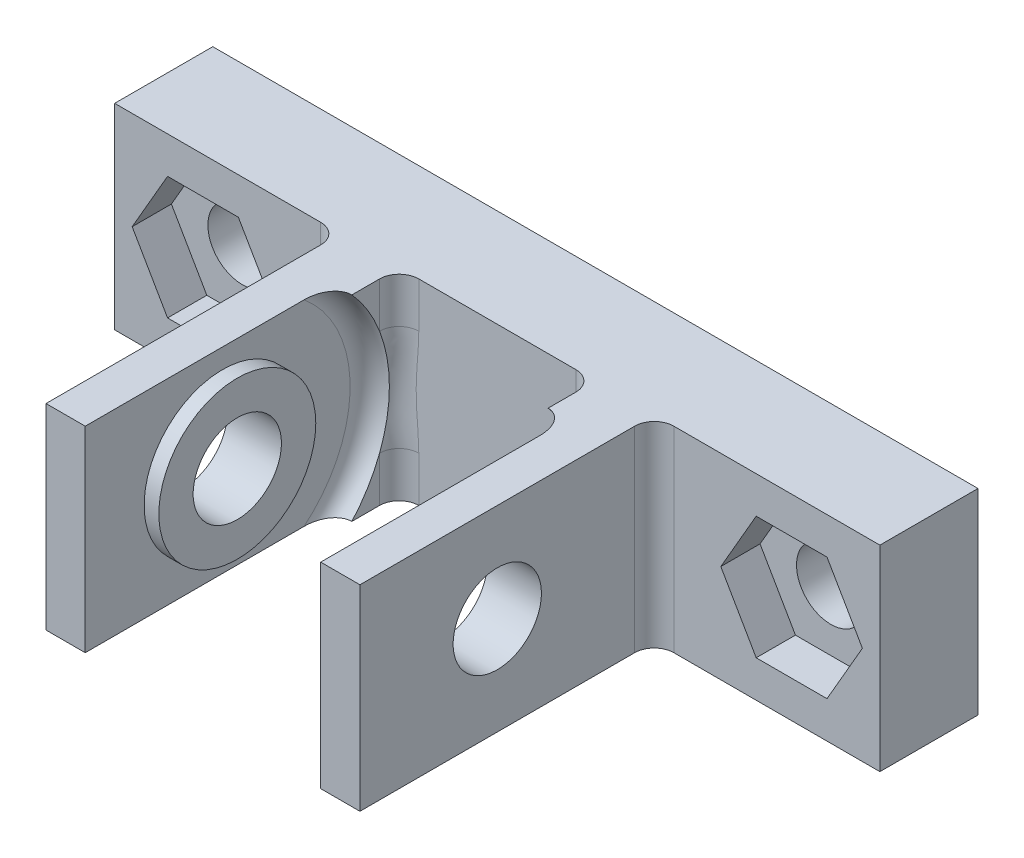
SolidWorks part; units mm, degrees
ref_plane "Front Plane" through (0, 0, 0) normal (0, 0, 1) x (1, 0, 0)
ref_plane "Top Plane" through (0, 0, 0) normal (0, 1, 0) x (1, 0, 0)
ref_plane "Right Plane" through (0, 0, 0) normal (1, 0, 0) x (0, 0, -1)
sketch "Sketch1" plane through (0, 0, 0) normal (0, 1, 0) x (1, 0, 0)
  line L0 (0, 0) -> (0, -20.0709) construction
  line L1 (-8, 0) -> (8, 0)
  line L2 (8, 0) -> (8, -20)
  line L3 (8, -20) -> (5, -20)
  line L4 (5, -20) -> (5, -5)
  line L5 (5, -5) -> (-5, -5)
  line L6 (-5, -20) -> (-5, -5)
  line L7 (-8, -20) -> (-5, -20)
  line L8 (-8, 0) -> (-8, -20)
  line L9 (5, -20) -> (5, -5)
  point P9 (0, -5)
  dimension "D1" = 5
  dimension "D2" = 3
  dimension "D3" = 15
  dimension "D4" = 5
extrude "Boss-Extrude1" add sketch "Sketch1" along normal blind 10 contours L1 L0 L5 L4 L3 L2 | L0 L1 L8 L7 L6 L5 region at (5.3235, 0, 7.7941) region at (-5.3235, 0, 7.7941)
sketch "Sketch2" plane through (8, 0, 0) normal (1, 0, 0) x (0, 0, -1)
  line L0 (-20, 5) -> (0, 5) construction
  line L1 (-20, 10) -> (-20, 0) construction
  line L2 (0, 10) -> (0, 0) construction
  circle A0 centre (-13, 5) radius 2.25
  dimension "D1" = 4.5
  dimension "D2" = 13
extrude "Cut-Extrude1" cut sketch "Sketch2" against normal through all contours A0
sketch "Sketch3" plane through (0, 10, 0) normal (0, 1, 0) x (1, 0, 0)
  line L1 (-19.5, -5) -> (19.5, -5)
  line L2 (0, 0) -> (0, -5) construction
  line L3 (-19.5, 0) -> (19.5, 0)
  line L4 (19.5, -5) -> (19.5, 0)
  line L5 (-8, 0) -> (8, 0) construction
  line L7 (-19.5, -5) -> (-19.5, 0)
  line L8 (5, -5) -> (-5, -5) construction
  dimension "D1" = 19.5
extrude "Boss-Extrude2" add sketch "Sketch3" against normal through all
sketch "Sketch4" plane through (0, 0, 5) normal (0, 0, 1) x (1, 0, 0)
  line L0 (-19.5, 5) -> (-8, 5) construction
  line L1 (-19.5, 0) -> (-19.5, 10) construction
  line L2 (-8, 10) -> (-8, 0) construction
  line L3 (-15, 0) -> (-15, 10) construction
  line L6 (0, 0) -> (0, 10) construction
  line L7 (5, 0) -> (-5, 0) construction
  line L8 (5, 10) -> (-5, 10) construction
  line L9 (15, 0) -> (15, 10) construction
  line L10 (19.5, 5) -> (8, 5) construction
  line L11 (-15, 0) -> (-15, 10) construction
  circle A0 centre (-15, 5) radius 1.75
  circle A1 centre (15, 5) radius 1.75
  dimension "D1" = 3.5
  dimension "D2" = 15
extrude "Cut-Extrude2" cut sketch "Sketch4" against normal through all
sketch "Sketch6" plane through (-5, 0, 0) normal (1, 0, 0) x (0, 0, -1)
  line L0 (-13, 12.5) -> (-20.5, 12.5)
  line L1 (-20.5, 12.5) -> (-20.5, 5)
  line L2 (-20.5, 5) -> (-20.5, -2.5)
  line L3 (-20.5, -2.5) -> (-13, -2.5)
  arc A0 (-13, -2.5) -> (-13, 12.5) centre (-13, 5) ccw
  circle A1 centre (-13, 5) radius 2.25 construction
  dimension "D1" = 15
extrude "Cut-Extrude3" cut sketch "Sketch6" against normal blind 1
sketch "Sketch5" plane through (-6, 0, 0) normal (1, 0, 0) x (0, 0, -1)
  circle A0 centre (-13, 5) radius 4
  circle A1 centre (-13, 5) radius 2.25
  circle A2 centre (-13, 5) radius 2.25 construction
  dimension "D1" = 8
extrude "Boss-Extrude3" add sketch "Sketch5" along normal blind 0.75
mirror "Mirror1" about plane through (0, 0, 0) normal (1, 0, 0) of "Boss-Extrude3", "Cut-Extrude3"
fillet "Fillet1" radius 1 6 edges at (-6, 5, 5.5) (6, 5, 5.5) (5, 5, 5) (-5, 5, 5) (8, 5, 5) (-8, 5, 5)
sketch "Sketch7" plane through (0, 0, 5) normal (0, 0, 1) x (1, 0, 0)
  line L0 (0, 10) -> (0, 0) construction
  line L1 (16.8042, 8.125) -> (13.1958, 8.125)
  line L2 (13.1958, 8.125) -> (11.3916, 5)
  line L3 (11.3916, 5) -> (13.1958, 1.875)
  line L4 (13.1958, 1.875) -> (16.8042, 1.875)
  line L5 (16.8042, 1.875) -> (18.6084, 5)
  line L6 (18.6084, 5) -> (16.8042, 8.125)
  line L7 (4, 10) -> (-4, 10) construction
  line L8 (-18.6084, 5) -> (-16.8042, 8.125)
  line L9 (-16.8042, 1.875) -> (-18.6084, 5)
  line L10 (-13.1958, 1.875) -> (-16.8042, 1.875)
  line L11 (-11.3916, 5) -> (-13.1958, 1.875)
  line L12 (-13.1958, 8.125) -> (-11.3916, 5)
  line L13 (-16.8042, 8.125) -> (-13.1958, 8.125)
  line L14 (18.6084, 5) -> (16.8042, 8.125)
  circle A0 centre (15, 5) radius 3.125 construction
  circle A1 centre (-15, 5) radius 3.125 construction
  circle M5 centre (15, 5) radius 1.75
  dimension "D1" = 6.25
extrude "Cut-Extrude4" cut sketch "Sketch7" against normal blind 2 contours L13 L8 L9 L10 L11 L12 | L5 L6 L1 L2 L3 L4 M5 | M5 region at (17.6236, 6.5148, 5) region at (-15, 5, 5) region at (15, 5, 5)
equation "\"X-ROD-SPACING\"=45"
equation "\"Y-ROD-SPACING\"=75"
equation "\"Z-ROD-SPACING\"=17.5"
equation "\"Y-BED-OFFSET\"=2"
equation "\"Y-BED-ROD-INSET\"=3.5"
equation "\"Y-BED-SCREW-SPACING\"=209"
equation "\"Y-BED-SCREW-CUTOUT-SLOT-HEIGHT\"=2"
equation "\"T-SLOT-NUT-FILLET-RADIUS\"=0.5"
equation "\"T-SLOT-SCREW-SHAFT-RADIUS\"=1.55"
equation "\"T-SLOT-SCREW-SHAFT-CUTOUT-LENGTH\"=11"
equation "\"T-SLOT-NUT-DEPTH\"=3.5"
equation "\"T-SLOT-NUT-WIDTH\"=2.85"
equation "\"T-SLOT-NUT-END-DISTANCE\"=8"
equation "\"ACRYLIC-THICKNESS\"=10"
equation "\"ACRYLIC-THICKNESS2\"=4.5"
equation "\"ACRYLIC-TAB-CUTOUT-SIZE\"=\"ACRYLIC-THICKNESS\"+\"ACRYLIC-TAB-TOLERANCE\"*2"
equation "\"ACRYLIC-TAB-TOLERANCE\"=-.05"
equation "\"KERF\"=0.075"
equation "\"ACRYLIC-THICKNESS-TAB-CUTOUT-WIDTH\"=\"ACRYLIC-THICKNESS\"-\"KERF\"*2"
equation "\"ACRYLIC-THICKNESS-TAB-CUTOUT-HEIGHT\"=\"ACRYLIC-TAB-WIDTH\"-\"KERF\"*4"
equation "\"ACRYLIC-THICKNESS2-TAB-CUTOUT-WIDTH\"=\"ACRYLIC-THICKNESS2\"-\"KERF\"*2"
equation "\"ACRYLIC-THICKNESS2-TAB-CUTOUT-HEIGHT\"=\"ACRYLIC-TAB-WIDTH\"-\"KERF\"*4"
equation "\"ACRYLIC-TAB-WIDTH\"=\"ACRYLIC-THICKNESS\""
equation "\"ACRYLIC-M3-HOLE\"=2.9"
equation "\"SMOOTHROD-CAP-SCREW-DISTANCE\"=20"
equation "\"FRAME-WIDTH-INNER\"=370"
equation "\"NEMA17-HOLE-SPACING\"=31"
equation "\"NEMA17-CENTRAL-CUTOUT\"=22.5"
equation "\"Z-BRACKET-REACH\"=57"
equation "\"Z-ROD-INSET\"=13.5"
equation "\"TOP-BRACKET-SPACING\"=40"
equation "\"SMOOTHROD-X-LENGTH\"=350"
equation "\"SMOOTHROD-Y-LENGTH\"=350"
equation "\"SMOOTHROD-Z-LENGTH\"=350"
equation "\"SMOOTHROD-TIGHTENING-HEADROOM\"=.25"
equation "\"LEADSCREW-Z-LENGTH\"=300"
equation "\"SCREW-LENGTH-FRAME\"=\"ACRYLIC-THICKNESS\" + 10"
equation "\"SCREW-LENGTH-MOTOR\"=\"ACRYLIC-THICKNESS\" + 5"
equation "\"SCREW-LENGTH-EXTRUDER\"=28"
equation "\"SCREW-HEAD-RADIUS\"=6"
equation "\"PRINTED-M3-HOLE\"=3.5"
equation "\"PRINTED-X-SMOOTHROD-DIAMETER\"=8.8"
equation "\"PRINTED-X-SMOOTHROD-CUTOUT\"=10"
equation "\"PRINTED-X-BASE-HEIGHT\"=10"
equation "\"PRINTED-LM8UU-CUTOUT-SIZE\"=15.5"
equation "\"PRINTED-LM8UU-CUTOUT-LENGTH\"=24.5"
equation "\"PRINTED-X-IDLER-HEIGHT\"=16"
equation "\"PRINTED-M3-NUT-AF\"=6.25"
equation "\"PSU-MOUNTING-WIDTH\"=95"
equation "\"PSU-MOUNTING-HEIGHT\"=177"
equation "\"Y-BELT-TO-ROD-DISTANCE\"=20"
equation "\"SPOOL-HOLDER-ROD-SPACING\"=150"
equation "\"ACRYLIC-X-CARRIAGE-WIDTH\"=55"
equation "\"ACRYLIC-X-CARRIAGE-HEIGHT\"=75"
equation "\"ACRYLIC-X-CARRIAGE-LM8UU-CUTOUT-WIDTH\"=24.25"
equation "\"ACRYLIC-X-CARRIAGE-LM8UU-CUTOUT-HEIGHT\"=11.0"
equation "\"ACRYLIC-X-CARRIAGE-SCREW-SPACING-X\"=15"
equation "\"ACRYLIC-X-CARRIAGE-SCREW-SPACING-Y\"=33"
equation "\"ACRYLIC-X-CARRIAGE-CENTER-TAB-SPACING\"=14"
equation "\"ACRYLIC-X-CARRIAGE-EXTRUDER-OFFSET\"=26"
equation "\"ACRYLIC-X-CARRIAGE-EXTRUDER-ANGLE\"=90"
equation "\"ACRYLIC-X-CARRIAGE-EXTRUDER-SHELF-DEPTH\"=\"ACRYLIC-X-CARRIAGE-EXTRUDER-OFFSET\" + 28"
equation "\"ACRYLIC-X-CARRIAGE-EXTRUDER-BRACE-SPACING\"=23"
equation "\"ACRYLIC-X-CARRIAGE-EXTRUDER-BRACE-TAB-OFFSET\"=20"
equation "\"ACRYLIC-X-CARRIAGE-EXTRUDER-BRACE-HEIGHT\"=35"
equation "\"ACRYLIC-X-CARRIAGE-EXTRUDER-BRACE-SCREW-SPACING\"=22"
equation "\"ACRYLIC-X-CARRIAGE-DUAL-WIDTH-MULTIPLIER\"=1.65"
equation "\"ACRYLIC-X-CARRIAGE-DUAL-HOTEND-SPACING\"=42"
equation "\"ACRYLIC-X-CARRIAGE-DUAL-WIDTH\"=75"
equation "\"ACRYLIC-X-CARRIAGE-DUAL-FAN-OFFSET\"=52"
equation "\"ACRYLIC-X-CARRIAGE-DUAL-FAN-HEIGHT\"=20"
equation "\"ACRYLIC-X-CARRIAGE-DUAL-HOTEND-SEPARATION\"=36"
equation "\"ACRYLIC-X-CARRIAGE-DUAL-MOUNT-PLATE-DEPTH\"=75"
equation "\"ACRYLIC-X-CARRIAGE-DUAL-MOUNT-BRACE-WIDTH\"=33"
equation "\"ACRYLIC-X-CARRIAGE-DUAL-MOUNT-SCREW-WIDTH\"=40"
equation "\"BLOWER-FAN-WIDTH\"=15"
equation "\"D1@Sketch7\"=\"PRINTED-M3-NUT-AF\""
